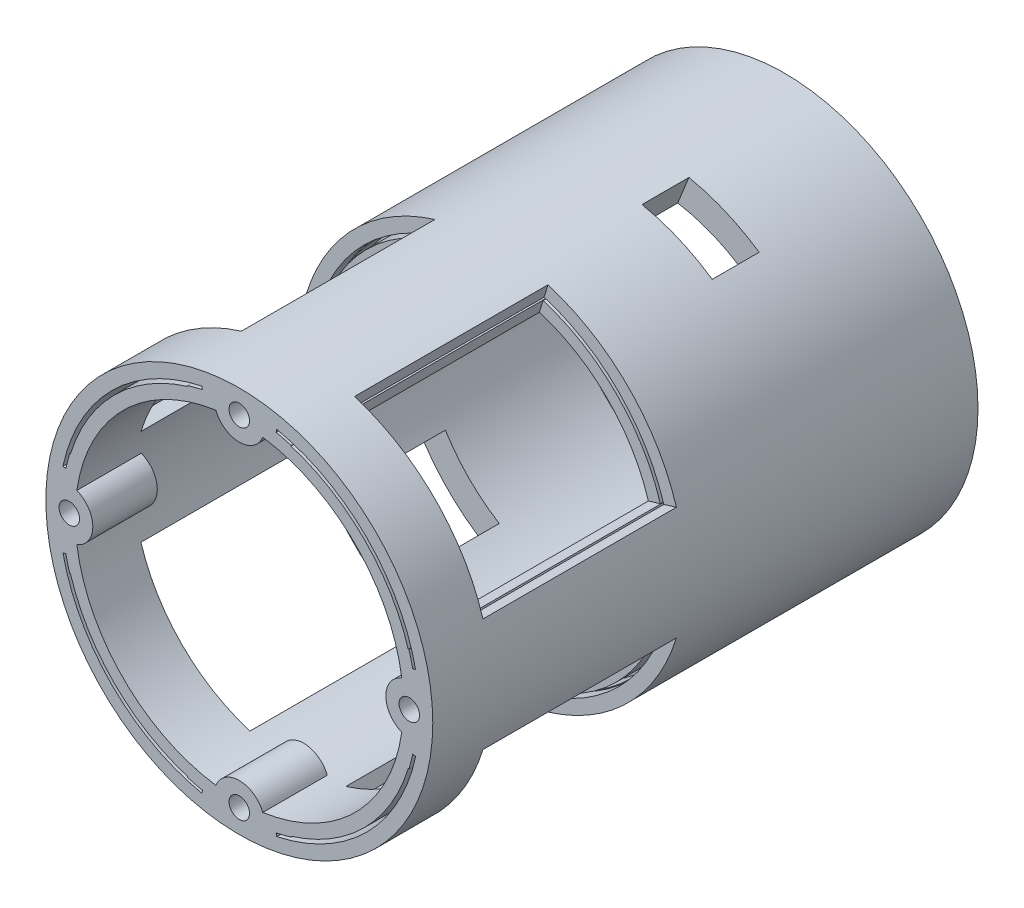
SolidWorks part; units mm, degrees
material "PEI"
ref_plane "Alzado" through (0, 0, 0) normal (0, 0, 1) x (1, 0, 0)
ref_plane "Planta" through (0, 0, 0) normal (0, 1, 0) x (1, 0, 0)
ref_plane "Vista lateral" through (0, 0, 0) normal (1, 0, 0) x (0, 0, -1)
sketch "Croquis1" plane through (0, 0, 0) normal (0, 0, 1) x (1, 0, 0)
  circle A0 centre (0, 0) radius 33
  circle A1 centre (0, 0) radius 28
  dimension "D1" = 66
  dimension "D2" = 5
extrude "Boss-Extrude1" add sketch "Croquis1" along normal blind 93
sketch "Croquis2" plane through (0, 0, 93) normal (0, 0, 1) x (1, 0, 0)
  line L0 (0, 0) -> (-6.3933, -30.078) construction
  line L1 (0, 0) -> (-30.078, -6.3933) construction
  line L2 (0, 0) -> (0, -30.5) construction
  line L3 (0, 0) -> (-30.5, 0) construction
  line L4 (-30.078, -6.3933) -> (-29.589, -6.2893)
  line L5 (-6.3933, -30.078) -> (-6.2893, -29.589)
  line L6 (-30.078, 6.3933) -> (-29.589, 6.2893)
  line L7 (-6.3933, 30.078) -> (-6.2893, 29.589)
  line L8 (6.3933, 30.078) -> (6.2893, 29.589)
  line L9 (30.078, 6.3933) -> (29.589, 6.2893)
  line L10 (30.078, -6.3933) -> (29.589, -6.2893)
  line L11 (6.3933, -30.078) -> (6.2893, -29.589)
  circle A0 centre (0, 0) radius 30.25 construction
  circle A1 centre (0, 0) radius 30.75 construction
  circle A2 centre (0, 0) radius 33 construction
  circle A3 centre (0, 0) radius 30.5 construction
  arc A4 (-6.3933, -30.078) -> (-30.078, -6.3933) centre (0, 0) cw
  arc A5 (-6.2893, -29.589) -> (-29.589, -6.2893) centre (0, 0) cw
  arc A6 (-30.078, 6.3933) -> (-6.3933, 30.078) centre (0, 0) cw
  arc A7 (-29.589, 6.2893) -> (-6.2893, 29.589) centre (0, 0) cw
  arc A8 (6.3933, 30.078) -> (30.078, 6.3933) centre (0, 0) cw
  arc A9 (6.2893, 29.589) -> (29.589, 6.2893) centre (0, 0) cw
  arc A10 (30.078, -6.3933) -> (6.3933, -30.078) centre (0, 0) cw
  arc A11 (29.589, -6.2893) -> (6.2893, -29.589) centre (0, 0) cw
  circle A12 centre (0, 0) radius 28 construction
  point P4 (-6.3413, -29.8335)
  point P32 (0, 0)
  dimension "D3" = 12
  dimension "D4" = 12
  dimension "D1" = 0.5
  dimension "D2" = 5
  dimension "D6" = 2.5
  dimension "D5" = 4
extrude "Cortar-Extruir1" cut sketch "Croquis2" against normal blind 45
ref_axis "Eje1" through (0, 0, 93) along (0, 0, -1)
ref_plane "Plano2" through (0, 0, 0) normal (0.9563, -0.2924, 0) x (0, 0, -1)
sketch "Croquis4" plane through (0, 0, 0) normal (0.9563, -0.2924, 0) x (0, 0, -1)
  line L0 (-83, 33) -> (-83, 30.6339)
  line L1 (0, 33) -> (-93, 33) construction
  line L2 (-83, 27.7679) -> (-50, 27.7679)
  line L3 (-50, 27.7679) -> (-50, 30.1339)
  line L4 (-50, 33) -> (-83, 33)
  line L5 (-97, 29) -> (-42, 29) construction
  line L6 (-93, 33) -> (-93, -33) construction
  line L7 (-93, 30.6339) -> (-83, 30.6339)
  line L8 (-45, 30.6339) -> (-45, 30.1339)
  line L9 (-45, 30.1339) -> (-50, 30.1339)
  line L10 (-93, 30.1339) -> (-93, 30.6339)
  line L11 (-83, 30.1339) -> (-93, 30.1339)
  line L12 (-83, 30.1339) -> (-83, 27.7679)
  line L13 (-50, 30.6339) -> (-45, 30.6339)
  line L14 (-50, 30.6339) -> (-50, 33)
  line L15 (-93, 30.633) -> (-93, 30.1349) construction
  point P20 (-93, 30.3839)
  point P21 (-93, 30.3839)
  dimension "D2" = 43
  dimension "D3" = 0.5
  dimension "D5" = 5
  dimension "D6" = 10
revolve "Cortar-Revolución2" cut sketch "Croquis4" angle 56 about axis through (0, 0, 93) along (0, 0, -1)
pattern_circular "MatrizC2" count 4 over 360 about axis through (0, 0, 93) along (0, 0, -1) of "Cortar-Revolución2"
sketch "Sketch8" plane through (0, 0, 0) normal (0, 0, -1) x (-1, 0, 0)
  arc A0 (-4, -27.7128) -> (4, -27.7128) centre (0, 0) ccw
  circle A1 centre (0, 0) radius 28 construction
  arc A2 (-4, -27.7128) -> (4, -27.7128) centre (0, -29.2908) cw
  arc A3 (-27.7128, 4) -> (-27.7128, -4) centre (0, 0) ccw
  arc A4 (-27.7128, 4) -> (-27.7128, -4) centre (-29.2908, 0) cw
  arc A5 (4, 27.7128) -> (-4, 27.7128) centre (0, 0) ccw
  arc A6 (4, 27.7128) -> (-4, 27.7128) centre (0, 29.2908) cw
  arc A7 (27.7128, -4) -> (27.7128, 4) centre (0, 0) ccw
  arc A8 (27.7128, -4) -> (27.7128, 4) centre (29.2908, 0) cw
  point P8 (0, -24.9908)
  point P20 (0, 0)
  dimension "D1" = 4.3
  dimension "D2" = 8
  dimension "D3" = 4
extrude "Boss-Extrude4" add sketch "Sketch8" against normal blind 11
sketch "Sketch9" plane through (0, 0, 0) normal (0, 0, -1) x (-1, 0, 0)
  circle A0 centre (0, -29) radius 1.75
  circle A1 centre (0, 0) radius 29 construction
  circle A2 centre (0, 0) radius 33 construction
  circle A3 centre (-29, 0) radius 1.75
  circle A4 centre (0, 29) radius 1.75
  circle A5 centre (29, 0) radius 1.75
  point P16 (0, 0)
  dimension "D1" = 4
  dimension "D2" = 3.5
  dimension "D3" = 4
extrude "Cut-Extrude3" cut sketch "Sketch9" against normal blind 10
ref_plane "Mid plane" through (0, 0, 46.5) normal (0, 0, 1) x (1, 0, 0)
mirror "Mirror1" about plane through (0, 0, 46.5) normal (0, 0, 1) of "Cut-Extrude3", "Boss-Extrude4"
ref_plane "Plano para USB y Switch" through (-23.3345, -23.3345, 0) normal (-0.7071, -0.7071, 0) x (0, 0, -1)
sketch "Sketch10" plane through (-23.3345, -23.3345, 0) normal (-0.7071, -0.7071, 0) x (0, 0, -1)
  line L0 (0, -33) -> (0, 33) construction
  line L1 (-10.5, 7.5) -> (-3.5, 7.5)
  line L2 (-10.5, 7.5) -> (-10.5, -7.5)
  line L3 (-10.5, -7.5) -> (-3.5, -7.5)
  line L4 (-3.5, 7.5) -> (-3.5, -7.5)
  line L5 (-10.5, 7.5) -> (-3.5, -7.5) construction
  line L6 (-10.5, -7.5) -> (-3.5, 7.5) construction
  line L8 (-42, 6.5) -> (-34, 6.5)
  line L9 (-42, 6.5) -> (-42, -6.5)
  line L10 (-42, -6.5) -> (-34, -6.5)
  line L11 (-34, 6.5) -> (-34, -6.5)
  line L12 (-42, 6.5) -> (-34, -6.5) construction
  line L13 (-42, -6.5) -> (-34, 6.5) construction
  point P0 (-7, 0)
  point P9 (-38, 0)
  dimension "D1" = 7
  dimension "D2" = 15
  dimension "D3" = 7
  dimension "D4" = 13
  dimension "D5" = 8
  dimension "D6" = 38
extrude "Corte USB y Switch" cut sketch "Sketch10" against normal blind 10
ref_plane "Plano USB PCB_C" through (12.362, 30.5971, 0) normal (0.3746, 0.9272, 0) x (0, 0, -1)
sketch "Sketch11" plane through (12.362, 30.5971, 0) normal (0.3746, 0.9272, 0) x (0, 0, -1)
  line L0 (0, -33) -> (0, 33) construction
  line L1 (-30.9, 6) -> (-22.9, 6)
  line L2 (-30.9, 6) -> (-30.9, -7)
  line L3 (-30.9, -7) -> (-22.9, -7)
  line L4 (-22.9, 6) -> (-22.9, -7)
  line L5 (-30.9, 6) -> (-22.9, -7) construction
  line L6 (-30.9, -7) -> (-22.9, 6) construction
  point P0 (-26.9, -0.5)
  dimension "D1" = 0.5
  dimension "D2" = 8
  dimension "D3" = 13
  dimension "D4" = 22.9
extrude "Cut-Extrude5" cut sketch "Sketch11" against normal blind 10
equation "\"D6@Croquis2\"=\"D2@Croquis2\"/2"
